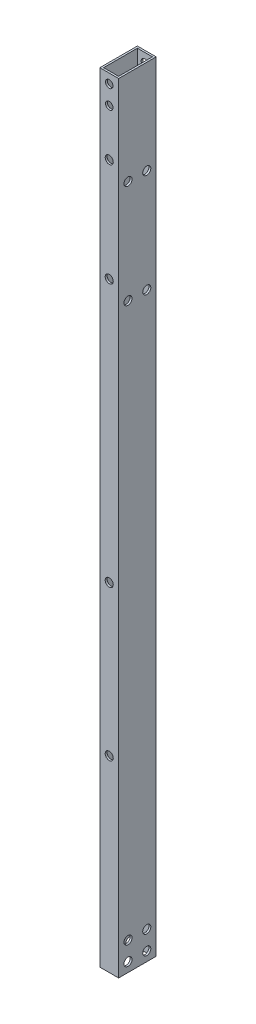
SolidWorks part; units mm, degrees
material "5052-H34"
ref_plane "正面" through (0, 0, 0) normal (0, 0, 1) x (1, 0, 0)
ref_plane "平面" through (0, 0, 0) normal (0, 1, 0) x (1, 0, 0)
ref_plane "右側面" through (0, 0, 0) normal (1, 0, 0) x (0, 0, -1)
sketch "ｽｹｯﾁ1" plane through (0, 0, 0) normal (0, 1, 0) x (1, 0, 0)
  line L1 (-5, 10) -> (5, 10)
  line L2 (-5, 10) -> (-5, -10)
  line L3 (-5, -10) -> (5, -10)
  line L4 (5, 10) -> (5, -10)
  line L5 (-5, 10) -> (5, -10) construction
  line L6 (-5, -10) -> (5, 10) construction
  point P0 (0, 0)
  dimension "D1" = 10
  dimension "D2" = 20
extrude "押し出し-薄板1" add sketch "ｽｹｯﾁ1" along normal blind 415 thin thin type one direction reverse wall 1
sketch "ｽｹｯﾁ2" plane through (5, 0, 0) normal (1, 0, 0) x (0, 0, -1)
  line L0 (5, 0) -> (5, 310) construction
  line L1 (10, 415) -> (10, 0) construction
  line L3 (-10, 0) -> (10, 0) construction
  line L4 (0, 415) -> (0, 0) construction
  line L5 (-10, 415) -> (10, 415) construction
  circle A0 centre (5, 310) radius 2.15
  circle A1 centre (5, 365) radius 2.15
  circle A3 centre (5, 5) radius 2.15
  circle A4 centre (5, 15) radius 2.15
  circle A5 centre (-5, 365) radius 2.15
  circle A6 centre (-5, 310) radius 2.15
  circle A7 centre (-5, 15) radius 2.15
  circle A8 centre (-5, 5) radius 2.15
  dimension "D1" = 4.3
  dimension "D5" = 4.3
  dimension "D3" = 295
  dimension "D2" = 55
  dimension "D6" = 5
  dimension "D7" = 10
  dimension "D8" = 5
extrude "ｶｯﾄ - 押し出し1" cut sketch "ｽｹｯﾁ2" against normal through all
sketch "ｽｹｯﾁ3" plane through (0, 0, 10) normal (0, 0, 1) x (1, 0, 0)
  line L0 (0, 0) -> (0, 320) construction
  line L1 (0, 415) -> (0, 375) construction
  line L2 (-5, 415) -> (5, 415) construction
  line L3 (0, 140) -> (5, 140) construction
  line L4 (5, 415) -> (5, 0) construction
  line L5 (-5, 0) -> (5, 0) construction
  circle A0 centre (0, 320) radius 2.15
  circle A1 centre (0, 375) radius 2.15
  circle A2 centre (0, 170) radius 2.15 construction
  circle A3 centre (0, 110) radius 2.15 construction
  circle A4 centre (0, 180) radius 2.15
  circle A5 centre (0, 100) radius 2.15
  circle A6 centre (0, 410) radius 2
  circle A7 centre (0, 400) radius 2
  dimension "D2" = 4.3
  dimension "D4" = 150
  dimension "D7" = 4.3
  dimension "D3" = 100
  dimension "D9" = 5
  dimension "D10" = 10
  dimension "D11" = 4
  dimension "D1" = 55
  dimension "D5" = 60
  dimension "D6" = 30
  dimension "D8" = 80
extrude "ｶｯﾄ - 押し出し2" cut sketch "ｽｹｯﾁ3" against normal through all
